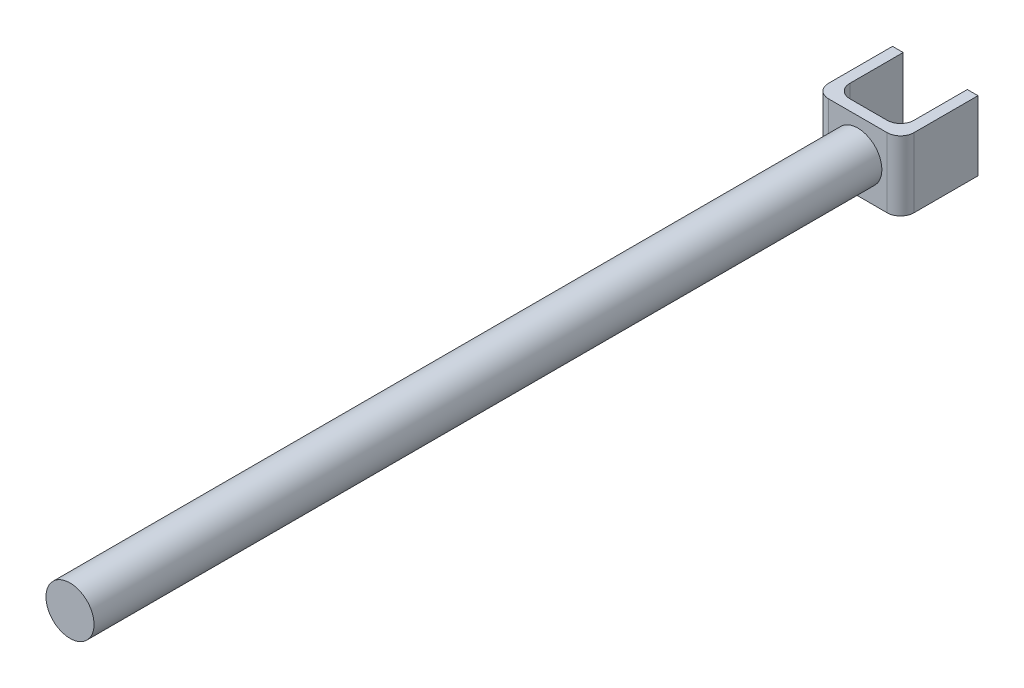
SolidWorks part; units mm, degrees
ref_plane "Front Plane" through (0, 0, 0) normal (0, 0, 1) x (1, 0, 0)
ref_plane "Top Plane" through (0, 0, 0) normal (0, 1, 0) x (1, 0, 0)
ref_plane "Right Plane" through (0, 0, 0) normal (1, 0, 0) x (0, 0, -1)
sketch "Sketch1" plane through (0, 0, 0) normal (0, 1, 0) x (1, 0, 0)
  line L0 (0, 0) -> (0, -20.7763) construction
  line L1 (7, -20.7763) -> (-7, -20.7763)
  line L2 (12, -15.7763) -> (12, 4.2237)
  line L3 (12, 4.2237) -> (16, 4.2237)
  line L4 (16, 4.2237) -> (16, -19.7763)
  line L5 (11, -24.7763) -> (-11, -24.7763)
  line L6 (-16, 4.2237) -> (-16, -19.7763)
  line L7 (-12, 4.2237) -> (-16, 4.2237)
  line L8 (-12, -15.7763) -> (-12, 4.2237)
  arc A0 (16, -19.7763) -> (11, -24.7763) centre (11, -19.7763) cw
  arc A1 (7, -20.7763) -> (12, -15.7763) centre (7, -15.7763) ccw
  arc A2 (-7, -20.7763) -> (-12, -15.7763) centre (-7, -15.7763) cw
  arc A3 (-16, -19.7763) -> (-11, -24.7763) centre (-11, -19.7763) ccw
  point P6 (0, -20.7763)
  point P13 (12, -20.7763)
  point P20 (0, -24.7763)
  point P22 (-12, -20.7763)
  dimension "D5" = 5
  dimension "D1" = 4
  dimension "D2" = 4
  dimension "D3" = 25
  dimension "D4" = 12
extrude "Boss-Extrude1" add sketch "Sketch1" along normal blind 13 and the other way blind 13
sketch "Sketch2" plane through (0, 0, 24.7763) normal (0, 0, 1) x (1, 0, 0)
  circle A0 centre (0, 0) radius 9
  dimension "D1" = 18
extrude "Boss-Extrude2" add sketch "Sketch2" along normal blind 295
sketch "Sketch3" plane through (0, 0, 0) normal (0, 1, 0) x (1, 0, 0)
  line L0 (0, 0) -> (0, -400) construction
  point P4 (0, -400)
  point P5 (0, 0)
  dimension "D1" = 400
